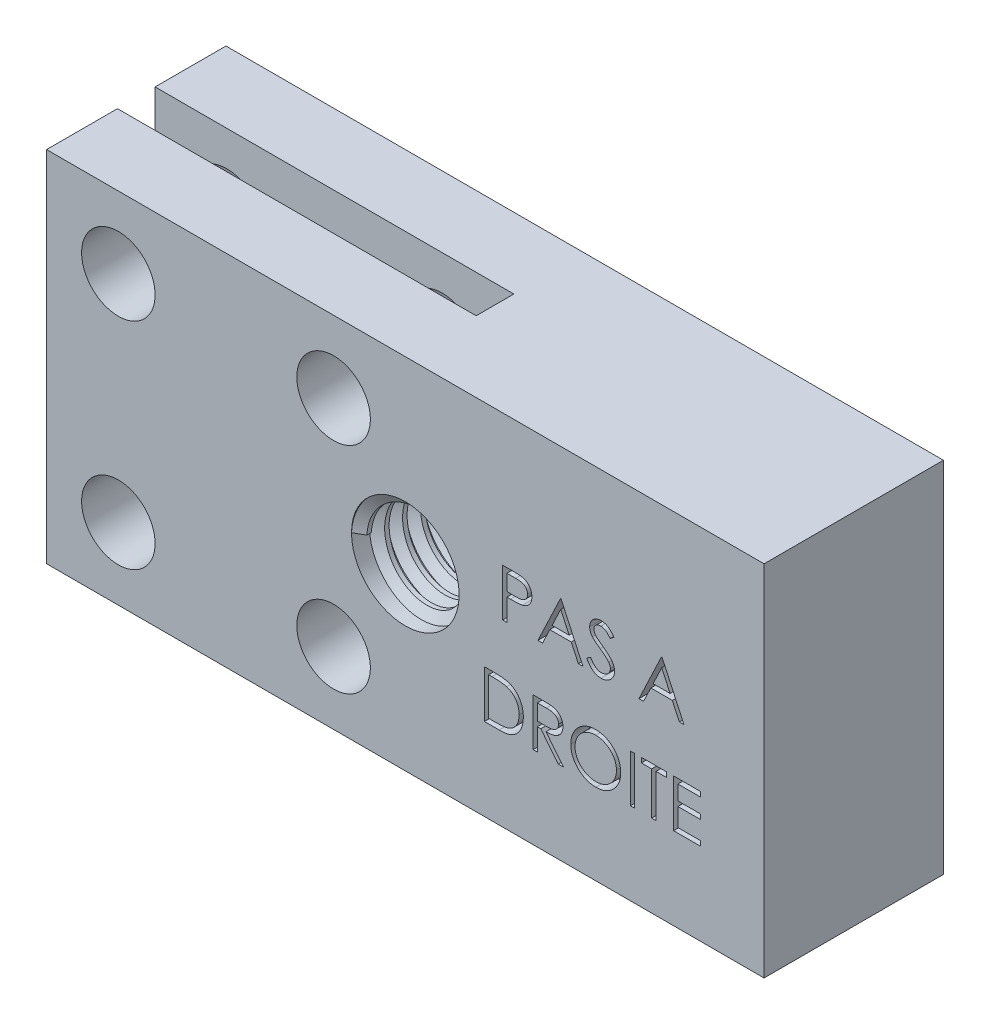
SolidWorks part; units mm, degrees
ref_plane "Plan de face" through (0, 0, 0) normal (0, 0, 1) x (1, 0, 0)
ref_plane "Plan de dessus" through (0, 0, 0) normal (0, 1, 0) x (1, 0, 0)
ref_plane "Plan de droite" through (0, 0, 0) normal (1, 0, 0) x (0, 0, -1)
sketch "Esquisse1" plane through (0, 0, 0) normal (0, 0, 1) x (1, 0, 0)
  line L1 (20, 10) -> (-20, 10)
  line L2 (20, 10) -> (20, -10)
  line L3 (20, -10) -> (-20, -10)
  line L4 (-20, 10) -> (-20, -10)
  line L5 (20, 10) -> (-20, -10) construction
  line L6 (20, -10) -> (-20, 10) construction
  point P0 (0, 0)
  dimension "D1" = 40
  dimension "D2" = 20
extrude "Boss.-Extru.1" add sketch "Esquisse1" along normal blind 10
sketch "Esquisse2" plane through (0, 0, 10) normal (0, 0, 1) x (1, 0, 0)
  circle A0 centre (0, 0) radius 3
  dimension "D1" = 6
extrude "Enlèv. mat.-Extru.1" cut sketch "Esquisse2" against normal blind 10
sketch "Esquisse3" plane through (0, -10, 0) normal (0, -1, 0) x (-1, 0, 0)
  line L0 (20, -10) -> (20, 0) construction
  line L1 (40, -6.05) -> (0, -6.05)
  line L2 (40, -6.05) -> (40, -3.95)
  line L3 (40, -3.95) -> (0, -3.95)
  line L4 (0, -6.05) -> (0, -3.95)
  line L5 (40, -6.05) -> (0, -3.95) construction
  line L6 (40, -3.95) -> (0, -6.05) construction
  point P0 (20, -5)
  dimension "D1" = 2.1
  dimension "D2" = 20
extrude "Enlèv. mat.-Extru.2" cut sketch "Esquisse3" against normal through all
sketch "Esquisse4" plane through (0, 0, 0) normal (0, 0, -1) x (-1, 0, 0)
  line L0 (-20, 10) -> (20, 10) construction
  line L1 (20, 10) -> (20, -10) construction
  line L2 (0, 10) -> (0, 3) construction
  line L3 (20, -10) -> (-20, -10) construction
  circle A0 centre (16, 6) radius 2.05
  circle A1 centre (4, 6) radius 2.05
  circle A2 centre (4, -6) radius 2.05
  circle A3 centre (16, -6) radius 2.05
  dimension "D1" = 4.1
  dimension "D2" = 4
  dimension "D3" = 4
  dimension "D4" = 4
  dimension "D5" = 4
extrude "Enlèv. mat.-Extru.3" cut sketch "Esquisse4" against normal through all
thread "Filetage1" pitch 1 method extrude profile "Profil de filetage1" start angle 0, offset 0, length 8.5, pitch 1, diameter 6
ref_plane "Plan1" through (-3, 0, 10) normal (0, -1, 0) x (-1, 0, 0)
sketch "Profil de filetage1" plane through (-3, 0, 10) normal (0, -1, 0) x (-1, 0, 0)
  line L0 (0, 0) -> (0, 1) construction
  line L11 (0, 0) -> (0, 0.875)
  line L12 (0, 0.875) -> (-0.5413, 0.5625)
  line L13 (-0.5413, 0.5625) -> (-0.5413, 0.3125)
  line L15 (-0.5413, 0.3125) -> (0, 0)
  line L17 (-0.5413, 0.4375) -> (0, 0.4375) construction
  point P2 (0, 0)
  dimension "Pitch" = 1
  dimension "Profile_Angle" = 60
  dimension "Profile_Land" = 0.25
  dimension "Profile_Height" = 0.5413
sketch "Esquisse8" plane through (0, 0, 10) normal (0, 0, 1) x (1, 0, 0)
  text T0 "     PAS A \r\n    DROITE" font "Century Gothic" height in points 10
extrude "Enlèv. mat.-Extru.4" cut sketch "Esquisse8" against normal blind 1
